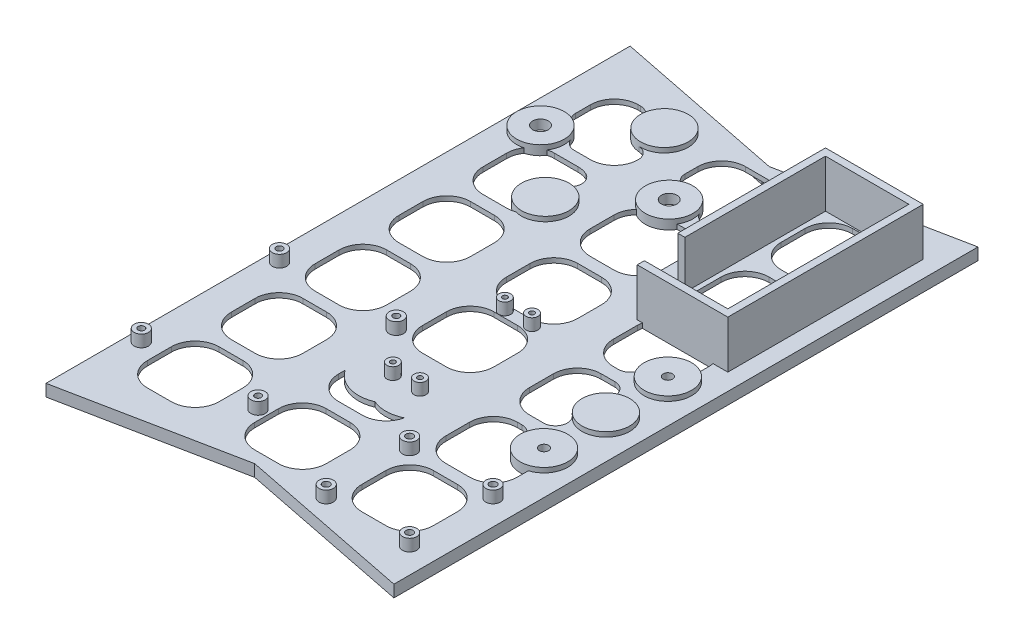
SolidWorks part; units mm, degrees
ref_plane "Front Plane" through (0, 0, 0) normal (0, 0, 1) x (1, 0, 0)
ref_plane "Top Plane" through (0, 0, 0) normal (0, 1, 0) x (1, 0, 0)
ref_plane "Right Plane" through (0, 0, 0) normal (1, 0, 0) x (0, 0, -1)
ref_axis "X" through (-88.99, 0, 0) along (1, 0, 0)
ref_axis "Y" through (0, 55, 0) along (0, -1, 0)
ref_axis "Z" through (0, 0, -88.99) along (0, 0, 1)
sketch "Sketch1" plane through (0, 0, 0) normal (0, 1, 0) x (1, 0, 0)
  line L0 (-75, 125) -> (0, 110) construction
  line L1 (-75, 125) -> (75, 125) construction
  line L2 (-75, 125) -> (-75, -125) construction
  line L3 (-75, -125) -> (75, -125) construction
  line L4 (75, 125) -> (75, -125) construction
  line L5 (-75, 125) -> (75, -125) construction
  line L6 (-75, -125) -> (75, 125) construction
  line L7 (0, 110) -> (75, 125) construction
  line L8 (-75, 0) -> (75, 0) construction
  line L9 (-75, -125) -> (0, -110) construction
  line L10 (0, -110) -> (75, -125) construction
  line L11 (-73, 122.5604) -> (-73, -122.5604)
  line L12 (-73, -122.5604) -> (0, -107.9604)
  line L13 (0, -107.9604) -> (73, -122.5604)
  line L14 (73, 122.5604) -> (73, -122.5604)
  line L15 (0, 107.9604) -> (73, 122.5604)
  line L16 (-73, 122.5604) -> (0, 107.9604)
  point P0 (0, 0)
  dimension "D1" = 250
  dimension "D2" = 150
  dimension "D3" = 15
  dimension "D4" = 2
extrude "Boss-Extrude1" add sketch "Sketch1" along normal blind 2
sketch "Sketch2" plane through (0, 2, 0) normal (0, 1, 0) x (1, 0, 0)
  line L0 (-73, 122.5604) -> (-73, -122.5604) construction
  line L1 (-50, -102.9604) -> (-40, -102.9604)
  line L2 (-60, -92.9604) -> (-60, -82.9604)
  line L3 (-50, -72.9604) -> (-40, -72.9604)
  line L4 (-30, -92.9604) -> (-30, -82.9604)
  line L5 (-15, -92.9604) -> (-15, -82.9604)
  line L6 (-5, -102.9604) -> (5, -102.9604)
  line L7 (15, -92.9604) -> (15, -82.9604)
  line L8 (-5, -72.9604) -> (5, -72.9604)
  line L9 (30, -92.9604) -> (30, -82.9604)
  line L10 (40, -102.9604) -> (50, -102.9604)
  line L11 (60, -92.9604) -> (60, -82.9604)
  line L12 (40, -72.9604) -> (50, -72.9604)
  line L73 (-60, -57.7762) -> (-60, -47.7762)
  line L74 (-50, -67.7762) -> (-40, -67.7762)
  line L75 (-30, -57.7762) -> (-30, -47.7762)
  line L76 (-50, -37.7762) -> (-40, -37.7762)
  line L77 (-15, -57.7762) -> (-15, -47.7762)
  line L78 (-5, -37.7762) -> (5, -37.7762)
  line L79 (15, -57.7762) -> (15, -47.7762)
  line L80 (-5, -67.7762) -> (5, -67.7762)
  line L81 (30, -57.7762) -> (30, -47.7762)
  line L82 (40, -37.7762) -> (50, -37.7762)
  line L83 (60, -57.7762) -> (60, -47.7762)
  line L84 (40, -67.7762) -> (50, -67.7762)
  line L85 (-60, -22.5921) -> (-60, -12.5921)
  line L86 (-50, -32.5921) -> (-40, -32.5921)
  line L87 (-30, -22.5921) -> (-30, -12.5921)
  line L88 (-50, -2.5921) -> (-40, -2.5921)
  line L89 (-15, -22.5921) -> (-15, -12.5921)
  line L90 (-5, -2.5921) -> (5, -2.5921)
  line L91 (15, -22.5921) -> (15, -12.5921)
  line L92 (-5, -32.5921) -> (5, -32.5921)
  line L93 (30, -22.5921) -> (30, -12.5921)
  line L94 (40, -2.5921) -> (50, -2.5921)
  line L95 (60, -22.5921) -> (60, -12.5921)
  line L96 (40, -32.5921) -> (50, -32.5921)
  line L97 (-60, 12.5921) -> (-60, 22.5921)
  line L98 (-50, 2.5921) -> (-40, 2.5921)
  line L99 (-30, 12.5921) -> (-30, 22.5921)
  line L100 (-50, 32.5921) -> (-40, 32.5921)
  line L101 (-15, 12.5921) -> (-15, 22.5921)
  line L102 (-5, 32.5921) -> (5, 32.5921)
  line L103 (15, 12.5921) -> (15, 22.5921)
  line L104 (-5, 2.5921) -> (5, 2.5921)
  line L105 (30, 12.5921) -> (30, 22.5921)
  line L106 (40, 32.5921) -> (50, 32.5921)
  line L107 (60, 12.5921) -> (60, 22.5921)
  line L108 (40, 2.5921) -> (50, 2.5921)
  line L109 (-60, 47.7762) -> (-60, 57.7762)
  line L110 (-50, 37.7762) -> (-40, 37.7762)
  line L111 (-30, 47.7762) -> (-30, 57.7762)
  line L112 (-50, 67.7762) -> (-40, 67.7762)
  line L113 (-15, 47.7762) -> (-15, 57.7762)
  line L114 (-5, 67.7762) -> (5, 67.7762)
  line L115 (15, 47.7762) -> (15, 57.7762)
  line L116 (-5, 37.7762) -> (5, 37.7762)
  line L117 (30, 47.7762) -> (30, 57.7762)
  line L118 (40, 67.7762) -> (50, 67.7762)
  line L119 (60, 47.7762) -> (60, 57.7762)
  line L120 (40, 37.7762) -> (50, 37.7762)
  line L121 (-60, 82.9604) -> (-60, 92.9604)
  line L122 (-50, 72.9604) -> (-40, 72.9604)
  line L123 (-30, 82.9604) -> (-30, 92.9604)
  line L124 (-50, 102.9604) -> (-40, 102.9604)
  line L125 (-15, 82.9604) -> (-15, 92.9604)
  line L126 (-5, 102.9604) -> (5, 102.9604)
  line L127 (15, 82.9604) -> (15, 92.9604)
  line L128 (-5, 72.9604) -> (5, 72.9604)
  line L129 (30, 82.9604) -> (30, 92.9604)
  line L130 (40, 102.9604) -> (50, 102.9604)
  line L131 (60, 82.9604) -> (60, 92.9604)
  line L132 (40, 72.9604) -> (50, 72.9604)
  arc A0 (-60, -92.9604) -> (-50, -102.9604) centre (-50, -92.9604) ccw
  arc A1 (-40, -102.9604) -> (-30, -92.9604) centre (-40, -92.9604) ccw
  arc A2 (-30, -82.9604) -> (-40, -72.9604) centre (-40, -82.9604) ccw
  arc A3 (-50, -72.9604) -> (-60, -82.9604) centre (-50, -82.9604) ccw
  arc A4 (60, -82.9604) -> (50, -72.9604) centre (50, -82.9604) ccw
  arc A5 (50, -102.9604) -> (60, -92.9604) centre (50, -92.9604) ccw
  arc A6 (40, -102.9604) -> (30, -92.9604) centre (40, -92.9604) cw
  arc A7 (30, -82.9604) -> (40, -72.9604) centre (40, -82.9604) cw
  arc A8 (-15, -82.9604) -> (-5, -72.9604) centre (-5, -82.9604) cw
  arc A9 (-15, -92.9604) -> (-5, -102.9604) centre (-5, -92.9604) ccw
  arc A10 (15, -92.9604) -> (5, -102.9604) centre (5, -92.9604) cw
  arc A11 (15, -82.9604) -> (5, -72.9604) centre (5, -82.9604) ccw
  arc A12 (-50, -37.7762) -> (-60, -47.7762) centre (-50, -47.7762) ccw
  arc A13 (-60, -57.7762) -> (-50, -67.7762) centre (-50, -57.7762) ccw
  arc A14 (-40, -67.7762) -> (-30, -57.7762) centre (-40, -57.7762) ccw
  arc A15 (-30, -47.7762) -> (-40, -37.7762) centre (-40, -47.7762) ccw
  arc A16 (-15, -57.7762) -> (-5, -67.7762) centre (-5, -57.7762) ccw
  arc A17 (-15, -47.7762) -> (-5, -37.7762) centre (-5, -47.7762) cw
  arc A18 (15, -47.7762) -> (5, -37.7762) centre (5, -47.7762) ccw
  arc A19 (15, -57.7762) -> (5, -67.7762) centre (5, -57.7762) cw
  arc A20 (30, -47.7762) -> (40, -37.7762) centre (40, -47.7762) cw
  arc A21 (40, -67.7762) -> (30, -57.7762) centre (40, -57.7762) cw
  arc A22 (60, -47.7762) -> (50, -37.7762) centre (50, -47.7762) ccw
  arc A23 (50, -67.7762) -> (60, -57.7762) centre (50, -57.7762) ccw
  arc A24 (-50, -2.5921) -> (-60, -12.5921) centre (-50, -12.5921) ccw
  arc A25 (-60, -22.5921) -> (-50, -32.5921) centre (-50, -22.5921) ccw
  arc A26 (-40, -32.5921) -> (-30, -22.5921) centre (-40, -22.5921) ccw
  arc A27 (-30, -12.5921) -> (-40, -2.5921) centre (-40, -12.5921) ccw
  arc A28 (-15, -22.5921) -> (-5, -32.5921) centre (-5, -22.5921) ccw
  arc A29 (-15, -12.5921) -> (-5, -2.5921) centre (-5, -12.5921) cw
  arc A30 (15, -12.5921) -> (5, -2.5921) centre (5, -12.5921) ccw
  arc A31 (15, -22.5921) -> (5, -32.5921) centre (5, -22.5921) cw
  arc A32 (30, -12.5921) -> (40, -2.5921) centre (40, -12.5921) cw
  arc A33 (40, -32.5921) -> (30, -22.5921) centre (40, -22.5921) cw
  arc A34 (60, -12.5921) -> (50, -2.5921) centre (50, -12.5921) ccw
  arc A35 (50, -32.5921) -> (60, -22.5921) centre (50, -22.5921) ccw
  arc A36 (-50, 32.5921) -> (-60, 22.5921) centre (-50, 22.5921) ccw
  arc A37 (-60, 12.5921) -> (-50, 2.5921) centre (-50, 12.5921) ccw
  arc A38 (-40, 2.5921) -> (-30, 12.5921) centre (-40, 12.5921) ccw
  arc A39 (-30, 22.5921) -> (-40, 32.5921) centre (-40, 22.5921) ccw
  arc A40 (-15, 12.5921) -> (-5, 2.5921) centre (-5, 12.5921) ccw
  arc A41 (-15, 22.5921) -> (-5, 32.5921) centre (-5, 22.5921) cw
  arc A42 (15, 22.5921) -> (5, 32.5921) centre (5, 22.5921) ccw
  arc A43 (15, 12.5921) -> (5, 2.5921) centre (5, 12.5921) cw
  arc A44 (30, 22.5921) -> (40, 32.5921) centre (40, 22.5921) cw
  arc A45 (40, 2.5921) -> (30, 12.5921) centre (40, 12.5921) cw
  arc A46 (60, 22.5921) -> (50, 32.5921) centre (50, 22.5921) ccw
  arc A47 (50, 2.5921) -> (60, 12.5921) centre (50, 12.5921) ccw
  arc A48 (-50, 67.7762) -> (-60, 57.7762) centre (-50, 57.7762) ccw
  arc A49 (-60, 47.7762) -> (-50, 37.7762) centre (-50, 47.7762) ccw
  arc A50 (-40, 37.7762) -> (-30, 47.7762) centre (-40, 47.7762) ccw
  arc A51 (-30, 57.7762) -> (-40, 67.7762) centre (-40, 57.7762) ccw
  arc A52 (-15, 47.7762) -> (-5, 37.7762) centre (-5, 47.7762) ccw
  arc A53 (-15, 57.7762) -> (-5, 67.7762) centre (-5, 57.7762) cw
  arc A54 (15, 57.7762) -> (5, 67.7762) centre (5, 57.7762) ccw
  arc A55 (15, 47.7762) -> (5, 37.7762) centre (5, 47.7762) cw
  arc A56 (30, 57.7762) -> (40, 67.7762) centre (40, 57.7762) cw
  arc A57 (40, 37.7762) -> (30, 47.7762) centre (40, 47.7762) cw
  arc A58 (60, 57.7762) -> (50, 67.7762) centre (50, 57.7762) ccw
  arc A59 (50, 37.7762) -> (60, 47.7762) centre (50, 47.7762) ccw
  arc A60 (-50, 102.9604) -> (-60, 92.9604) centre (-50, 92.9604) ccw
  arc A61 (-60, 82.9604) -> (-50, 72.9604) centre (-50, 82.9604) ccw
  arc A62 (-40, 72.9604) -> (-30, 82.9604) centre (-40, 82.9604) ccw
  arc A63 (-30, 92.9604) -> (-40, 102.9604) centre (-40, 92.9604) ccw
  arc A64 (-15, 82.9604) -> (-5, 72.9604) centre (-5, 82.9604) ccw
  arc A65 (-15, 92.9604) -> (-5, 102.9604) centre (-5, 92.9604) cw
  arc A66 (15, 92.9604) -> (5, 102.9604) centre (5, 92.9604) ccw
  arc A67 (15, 82.9604) -> (5, 72.9604) centre (5, 82.9604) cw
  arc A68 (30, 92.9604) -> (40, 102.9604) centre (40, 92.9604) cw
  arc A69 (40, 72.9604) -> (30, 82.9604) centre (40, 82.9604) cw
  arc A70 (60, 92.9604) -> (50, 102.9604) centre (50, 92.9604) ccw
  arc A71 (50, 72.9604) -> (60, 82.9604) centre (50, 82.9604) ccw
  point P81 (-30, -102.9604)
  point P84 (-30, -72.9604)
  point P87 (-60, -72.9604)
  dimension "D9" = 10
  dimension "D7" = 10
  dimension "D1" = 30
  dimension "D2" = 30
  dimension "D3" = 13
  dimension "D4" = 5
  dimension "D6" = 15
  dimension "D8" = 6
  dimension "D10" = 5
  dimension "D5" = 3
extrude "Cut-Extrude1" cut sketch "Sketch2" against normal through all
sketch "Sketch3" plane through (0, 2, 0) normal (0, 1, 0) x (1, 0, 0)
  line L1 (-73, 122.5604) -> (-73, -122.5604) construction
  circle A0 centre (-68, -29.5604) radius 3
  circle A1 centre (-19, -29.5604) radius 3
  circle A2 centre (-68, -87.5604) radius 3
  circle A3 centre (-19, -87.5604) radius 3
  dimension "D1" = 6
  dimension "D2" = 49
  dimension "D3" = 58
  dimension "D4" = 5
  dimension "D5" = 35
extrude "Boss-Extrude2" add sketch "Sketch3" along normal blind 5 and the other way through all
sketch "Sketch4" plane through (0, 7, 0) normal (0, 1, 0) x (1, 0, 0)
  circle A1 centre (-19, -87.5604) radius 1.35
  circle A2 centre (-68, -87.5604) radius 1.35
  circle A3 centre (-68, -29.5604) radius 1.35
  circle A4 centre (-19, -29.5604) radius 1.35
  dimension "D1" = 2.7
extrude "Cut-Extrude2" cut sketch "Sketch4" against normal through all
sketch "Sketch5" plane through (0, 2, 0) normal (0, 1, 0) x (1, 0, 0)
  line L0 (30, -87.9604) -> (60, -87.9604) construction
  line L1 (30, -82.9604) -> (30, -92.9604) construction
  line L2 (60, -92.9604) -> (60, -82.9604) construction
  circle A0 centre (27.5, -70.4604) radius 3
  circle A2 centre (62.5, -70.4604) radius 3
  circle A4 centre (62.5, -105.4604) radius 3
  circle A6 centre (27.5, -105.4604) radius 3
  circle A9 centre (45, -87.9604) radius 24.7487 construction
  dimension "D2" = 6
  dimension "D3" = 35
  dimension "D4" = 35
extrude "Boss-Extrude3" add sketch "Sketch5" along normal blind 5
sketch "Sketch6" plane through (0, 7, 0) normal (0, 1, 0) x (1, 0, 0)
  circle A0 centre (27.5, -70.4604) radius 1.5
  circle A1 centre (62.5, -70.4604) radius 1.5
  circle A2 centre (62.5, -105.4604) radius 1.5
  circle A3 centre (27.5, -105.4604) radius 1.5
  dimension "D1" = 3
extrude "Cut-Extrude3" cut sketch "Sketch6" against normal through all
sketch "Sketch7" plane through (0, 2, 0) normal (0, 1, 0) x (1, 0, 0)
  line L0 (73, -122.5604) -> (73, 122.5604) construction
  line L1 (30, -17.5921) -> (73, -17.5921) construction
  line L2 (30, -12.5921) -> (30, -22.5921) construction
  line L3 (57, 8.4079) -> (57, -43.5921) construction
  circle A0 centre (57, -43.5921) radius 10
  circle A1 centre (57, 8.4079) radius 10
  circle A2 centre (57, -17.5921) radius 10
  point P6 (51.5, -17.5921)
  point P13 (57, -17.5921)
  dimension "D1" = 20
  dimension "D2" = 16
  dimension "D3" = 52
extrude "Boss-Extrude4" add sketch "Sketch7" along normal blind 2 and the other way through all
sketch "Sketch8" plane through (0, 4, 0) normal (0, 1, 0) x (1, 0, 0)
  circle A0 centre (57, 8.4079) radius 1.95
  circle A1 centre (57, -43.5921) radius 1.95
  dimension "D1" = 3.9
extrude "Cut-Extrude4" cut sketch "Sketch8" against normal through all
sketch "Sketch9" plane through (0, 2, 0) normal (0, 1, 0) x (1, 0, 0)
  line L0 (73, 0) -> (-73, 0) construction
  line L1 (73, -122.5604) -> (73, 122.5604) construction
  line L2 (-73, 122.5604) -> (-73, -122.5604) construction
  circle A0 centre (-3, 0) radius 2.5
  circle A1 centre (-3, -47) radius 2.5
  circle A2 centre (8.4, -47) radius 2.5
  circle A3 centre (8.4, 0) radius 2.5
  point P14 (3.1945, 0)
  dimension "D1" = 5
  dimension "D4" = 70
  dimension "D2" = 11.4
  dimension "D3" = 47
extrude "Boss-Extrude5" add sketch "Sketch9" along normal blind 5
sketch "Sketch16" plane through (0, 2, 0) normal (0, -1, 0) x (1, 0, 0)
  line L0 (-5, 32.5921) -> (5, 32.5921) construction
  circle A0 centre (8.4, 47) radius 14.4079
  circle A1 centre (-3, 47) radius 14.4079
  circle M3 centre (8.4, 47) radius 2.5
extrude "Boss-Extrude10" add sketch "Sketch16" along normal up to surface (2 mm away) contours A0 A1 | A0 A1 M3 | M3 | A1 A0 region at (14.3268, 2, 47) region at (2.3422, 2, 47) region at (-8.9268, 2, 47) region at (8.4, 2, 47) up to face at (57, 0, -6.4579)
sketch "Sketch10" plane through (0, 7, 0) normal (0, 1, 0) x (1, 0, 0)
  circle A0 centre (8.4, 0) radius 1.05
  circle A1 centre (8.4, -47) radius 1.05
  circle A2 centre (-3, -47) radius 1.05
  circle A3 centre (-3, 0) radius 1.05
  dimension "D1" = 2.1
extrude "Cut-Extrude5" cut sketch "Sketch10" against normal through all
sketch "Sketch11" plane through (0, 2, 0) normal (0, 1, 0) x (1, 0, 0)
  line L0 (-73, 122.5604) -> (-73, -122.5604) construction
  line L1 (-34, 97.9604) -> (-34, 47.9604) construction
  line L2 (-61, 72.9604) -> (-7, 72.9604) construction
  circle A3 centre (-7, 72.9604) radius 10
  circle A4 centre (-61, 72.9604) radius 10
  circle A5 centre (-34, 97.9604) radius 10
  circle A6 centre (-34, 47.9604) radius 10
  point P11 (-34, 72.9604)
  dimension "D1" = 20
  dimension "D2" = 54
  dimension "D3" = 35
  dimension "D4" = 12
  dimension "D5" = 50
extrude "Boss-Extrude6" add sketch "Sketch11" along normal blind 2 and the other way through all
sketch "Sketch12" plane through (0, 4, 0) normal (0, 1, 0) x (1, 0, 0)
  circle A0 centre (-61, 72.9604) radius 3.25
  circle A1 centre (-7, 72.9604) radius 3.25
  dimension "D1" = 6.5
extrude "Cut-Extrude6" cut sketch "Sketch12" against normal through all
sketch "Sketch13" plane through (0, 2, 0) normal (0, 1, 0) x (1, 0, 0)
  line L0 (28, 24.5604) -> (66, 24.5604)
  line L1 (66, 24.5604) -> (66, 106.5604)
  line L2 (66, 106.5604) -> (25, 106.5604)
  line L3 (25, 106.5604) -> (25, 44.5604)
  line L4 (25, 44.5604) -> (28, 44.5604)
  line L5 (28, 44.5604) -> (28, 103.5604)
  line L6 (28, 103.5604) -> (63, 103.5604)
  line L7 (63, 103.5604) -> (63, 27.5604)
  line L8 (63, 27.5604) -> (28, 27.5604)
  line L9 (28, 27.5604) -> (28, 24.5604)
  line L10 (73, -122.5604) -> (73, 122.5604) construction
  dimension "D1" = 62
  dimension "D2" = 3
  dimension "D3" = 3
  dimension "D4" = 3
  dimension "D5" = 3
  dimension "D6" = 35
  dimension "D7" = 76
  dimension "D8" = 16
  dimension "D9" = 7
extrude "Boss-Extrude7" add sketch "Sketch13" along normal blind 20 and the other way through all
fillet "Fillet2" radius 5 11 edges at (48.8651, 1, -2.5921) (48.8651, 1, 37.7762) (58.7473, 1, 27.4382) (58.7473, 1, 7.7459) (-30, 1, -57.1255) (-14.4353, 1, -79.6474) (3, 1, -72.9604) (-59.9999, 1, -82.9103) (-51.0001, 1, -73.0105) (-42.6603, 1, -102.9604) (-30, 1, -88.7952)
sketch "Sketch15" plane through (0, 0, 0) normal (0, -1, 0) x (1, 0, 0)
  line L0 (0, 107.9604) -> (73, 122.5604) construction
  line L1 (-73, 122.5604) -> (0, 107.9604) construction
  line L2 (73, 122.5604) -> (73, -122.5604) construction
  line L3 (73, -122.5604) -> (0, -107.9604) construction
  line L4 (0, -107.9604) -> (-73, -122.5604) construction
  line L5 (-73, -122.5604) -> (-73, 122.5604) construction
  line L6 (0, 107.9604) -> (73, 122.5604)
  line L7 (-73, 122.5604) -> (0, 107.9604)
  line L8 (73, 122.5604) -> (73, -122.5604)
  line L9 (73, -122.5604) -> (0, -107.9604)
  line L10 (0, -107.9604) -> (-73, -122.5604)
  line L11 (-73, -122.5604) -> (-73, 122.5604)
  line L12 (0, 104.901) -> (70, 118.901)
  line L13 (70, 118.901) -> (70, -118.901)
  line L14 (70, -118.901) -> (0, -104.901)
  line L15 (0, -104.901) -> (-70, -118.901)
  line L16 (-70, -118.901) -> (-70, 118.901)
  line L17 (-70, 118.901) -> (0, 104.901)
  dimension "D1" = 3
extrude "Boss-Extrude9" add sketch "Sketch15" along normal blind 3
